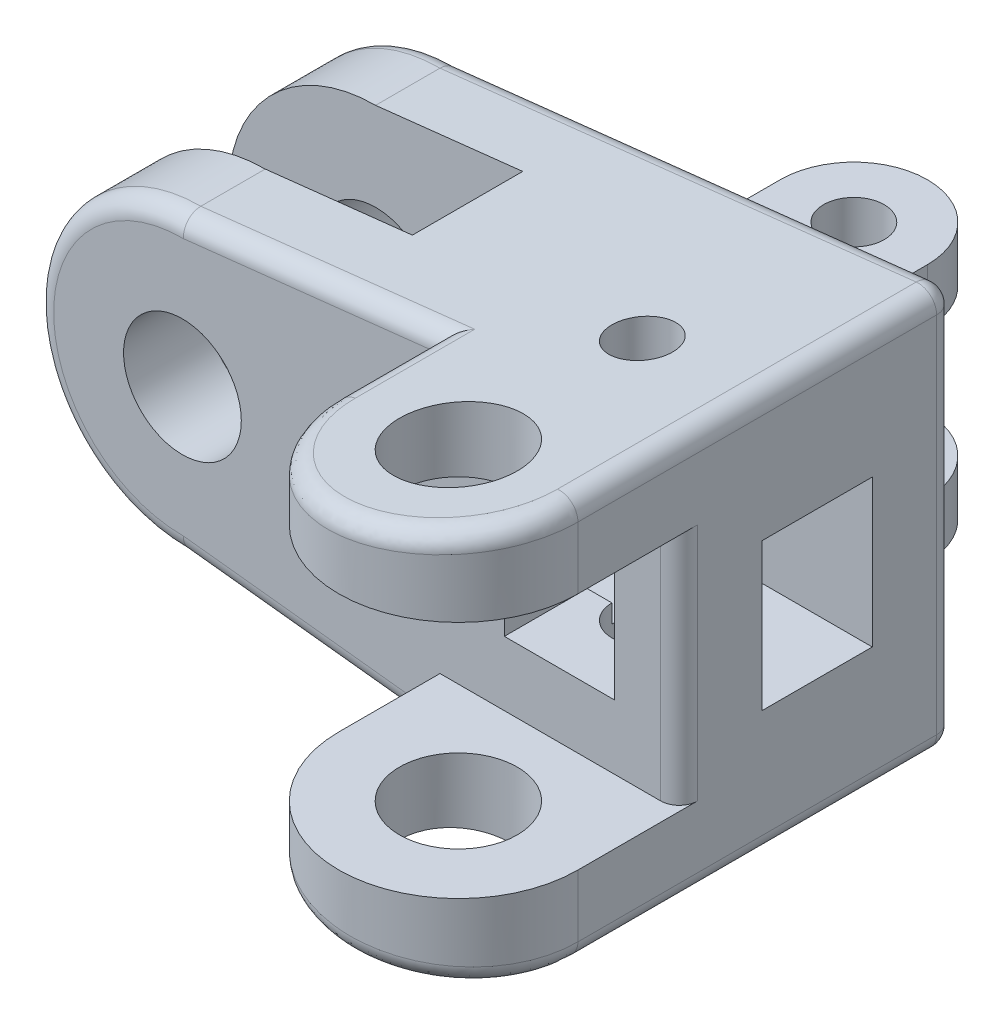
SolidWorks part; units mm, degrees
ref_plane "Front Plane" through (0, 0, 0) normal (0, 0, 1) x (1, 0, 0)
ref_plane "Top Plane" through (0, 0, 0) normal (0, 1, 0) x (1, 0, 0)
ref_plane "Right Plane" through (0, 0, 0) normal (1, 0, 0) x (0, 0, -1)
sketch "Sketch1" plane through (0, 0, 0) normal (0, 0, 1) x (1, 0, 0)
  line L0 (8.0231, 57.826) -> (8.0231, 60.826)
  line L1 (8.0231, 41.826) -> (8.0231, 38.826)
  line L2 (-18.9769, 41.826) -> (8.0231, 38.826)
  line L3 (8.0231, 42.326) -> (8.0231, 57.326)
  line L4 (-18.9769, 57.826) -> (8.0231, 60.826)
  line L6 (8.0231, 57.826) -> (8.0231, 57.326)
  line L8 (8.0231, 41.826) -> (8.0231, 42.326)
  circle A0 centre (-18.9769, 49.826) radius 3.2
  arc A1 (-18.9769, 57.826) -> (-18.9769, 41.826) centre (-18.9769, 49.826) ccw
extrude "Boss-Extrude1" add sketch "Sketch1" along normal blind 15
sketch "Sketch6" plane through (0, 0, 15) normal (0, 0, 1) x (1, 0, 0)
  line L2 (-4.9769, 49.826) -> (-4.9769, 59.3815)
  line L3 (8.0231, 60.826) -> (-18.9769, 57.826) construction
  line L4 (-4.9769, 59.3815) -> (8.0231, 60.826)
  line L5 (8.0231, 60.826) -> (8.0231, 38.826)
  line L6 (8.0231, 38.826) -> (-4.9769, 40.2704)
  line L7 (-18.9769, 41.826) -> (8.0231, 38.826) construction
  line L8 (-4.9769, 40.2704) -> (-4.9769, 49.826)
extrude "Boss-Extrude3" add sketch "Sketch6" along normal blind 12
sketch "Sketch9" plane through (0, 0, 0) normal (0, 1, 0) x (1, 0, 0)
  line L3 (8.0231, -20.5) -> (8.0231, -27)
  line L4 (8.0231, -27) -> (-4.9769, -27)
  line L5 (-4.9769, -27) -> (-4.9769, -20.5)
  arc A0 (-4.9769, -20.5) -> (8.0231, -20.5) centre (1.5231, -20.5) ccw
  circle A1 centre (1.5231, -20.5) radius 3.2
  circle A2 centre (1.5231, -10.5) radius 1.65
extrude "Cut-Extrude2" cut sketch "Sketch9" along normal blind 24 from offset 38 contours A1 | A0 L5 L4 | A0 L4 L3 | A2 region at (-3.525, 0, 25.5481) region at (6.5712, 0, 25.5481) region at (1.5231, 0, 20.5) region at (1.5231, 0, 10.5)
sketch "Sketch11" plane through (-4.9769, 0, 0) normal (-1, 0, 0) x (0, 0, 1)
  line L2 (27, 39.5482) -> (27, 60.1038) construction
  line L3 (27, 49.826) -> (27, 56.326)
  line L4 (27, 49.826) -> (27, 43.326)
  line L5 (27, 56.326) -> (15, 56.326)
  line L7 (15, 59.3815) -> (15, 40.2704) construction
  line L8 (15, 56.326) -> (15, 43.326)
  line L9 (15, 41.826) -> (15, 57.826) construction
  line L10 (15, 43.326) -> (27, 43.326)
extrude "Cut-Extrude3" cut sketch "Sketch11" against normal blind 13
sketch "Sketch12" plane through (0, 0, 0) normal (0, 0, -1) x (-1, 0, 0)
  line L1 (1.4769, 53.826) -> (-2.5231, 53.826)
  line L2 (-2.5231, 53.826) -> (-2.5231, 56.826)
  line L3 (-2.5231, 56.826) -> (1.4769, 56.826)
  line L4 (1.4769, 53.826) -> (5.4769, 53.826)
  line L5 (5.4769, 53.826) -> (5.4769, 56.826)
  line L6 (5.4769, 56.826) -> (1.4769, 56.826)
  line L7 (1.4769, 42.826) -> (-2.5231, 42.826)
  line L8 (-2.5231, 42.826) -> (-2.5231, 45.826)
  line L9 (1.4769, 45.826) -> (5.4769, 45.826)
  line L10 (5.4769, 45.826) -> (5.4769, 42.826)
  line L11 (-2.5231, 45.826) -> (1.4769, 45.826)
  line L12 (5.4769, 42.826) -> (1.4769, 42.826)
extrude "Boss-Extrude4" add sketch "Sketch12" along normal blind 8
sketch "Sketch14" plane through (0, 56.826, 0) normal (0, 1, 0) x (1, 0, 0)
  line L3 (-5.4769, 4) -> (-5.4769, 8)
  line L4 (-5.4769, 8) -> (-5.4769, 0) construction
  line L5 (-5.4769, 8) -> (2.5231, 8)
  line L6 (2.5231, 8) -> (2.5231, 4)
  arc A0 (2.5231, 4) -> (-5.4769, 4) centre (-1.4769, 4) ccw
  circle A1 centre (-1.4769, 4) radius 1.65
  line M2 (2.5231, 0) -> (2.5231, 8)
  line M3 (2.5231, 8) -> (-5.4769, 8)
  line M4 (-5.4769, 8) -> (-5.4769, 0)
extrude "Cut-Extrude4" cut sketch "Sketch14" against normal blind 14 contours A0 M2 M3 | A0 L5 M4 | A1 region at (1.6296, 56.826, -7.1065) region at (-4.5835, 56.826, -7.1065) region at (-1.4769, 56.826, -4)
sketch "Sketch19" plane through (0, 0, 0) normal (0, 1, 0) x (1, 0, 0)
  line L0 (-10.9769, -10.5) -> (-10.9769, -4.5)
  line L1 (-10.9769, -10.5) -> (-10.9769, -4.5)
  line L3 (-10.9769, -4.5) -> (-10.9769, -7.5)
  line L5 (-28.9769, -7.5) -> (-28.9769, -4.5)
  line L6 (-28.9769, -4.5) -> (-10.9769, -4.5)
  line L7 (-28.9769, -7.5) -> (-28.9769, -10.5)
  line L9 (-10.9769, -10.5) -> (-28.9769, -10.5)
extrude "Cut-Extrude7" cut sketch "Sketch19" along normal blind 20 from offset 40 contours L9 L0 L1 L6 L5 L7 region at (-19.9769, 0, 7.5)
sketch "Sketch20" plane through (-10.9769, 0, 0) normal (-1, 0, 0) x (0, 0, 1)
  line L0 (4.5, 53.826) -> (10.5, 53.826)
  line L2 (10.5, 58.7149) -> (10.5, 40.9371) construction
  line L3 (10.5, 53.826) -> (4.5, 53.826)
  line L4 (4.5, 41.826) -> (4.5, 57.826) construction
  line L5 (10.5, 53.826) -> (10.5, 45.826)
  line L7 (4.5, 45.826) -> (10.5, 45.826)
  line L8 (10.5, 57.826) -> (10.5, 41.826) construction
  line L9 (10.5, 45.826) -> (10.5, 53.826)
  line L10 (4.5, 53.826) -> (4.5, 45.826)
  line M2 (4.5, 58.7149) -> (4.5, 40.9371)
  line M4 (10.5, 40.9371) -> (10.5, 58.7149)
extrude "Cut-Extrude8" cut sketch "Sketch20" against normal blind 20 contours L7 L0 M2 M4 region at (-10.9769, 49.826, 7.5)
sketch "Sketch21" plane through (0, 0, 15) normal (0, 0, 1) x (1, 0, 0)
  line L5 (4.5231, 49.826) -> (4.5231, 52.826)
  line L6 (4.5231, 52.826) -> (-1.4769, 52.826)
  line L7 (-1.4769, 52.826) -> (-1.4769, 46.826)
  line L8 (-1.4769, 46.826) -> (4.5231, 46.826)
  line L9 (4.5231, 46.826) -> (4.5231, 49.826)
extrude "Cut-Extrude9" cut sketch "Sketch21" against normal blind 5
fillet "Fillet2" radius 1 14 edges at (1.5231, 60.1038, 27) (1.5231, 39.5482, 27) (-26.9769, 49.826, 15) (-26.9769, 49.826, 0) (-5.4769, 59.326, 0) (-5.4769, 40.326, 0) (8.0231, 60.826, 10.25) (8.0231, 49.826, 15) (8.0231, 38.826, 10.25) (8.0231, 49.826, 0)
